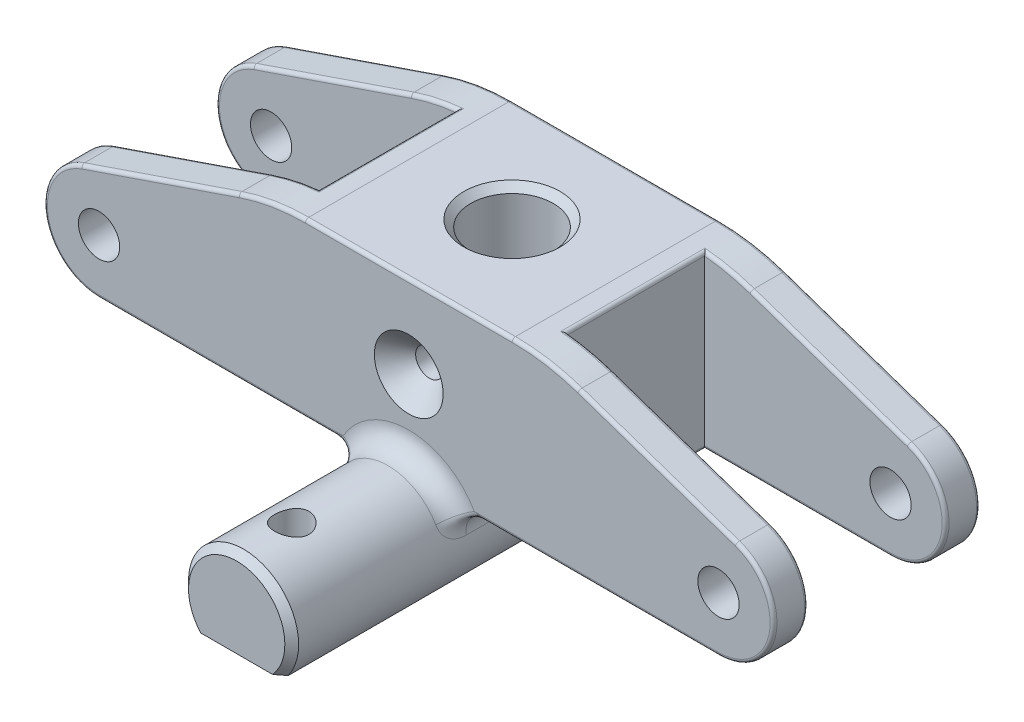
SolidWorks part; units mm, degrees
note: The reader was unsure of these and kept them because the rebuilt part matched: shared geometry of "Sketch2<3>", "Sketch4<3>".
material "Nickel"
ref_plane "Front Plane" through (0, 0, 0) normal (0, 0, 1) x (1, 0, 0)
ref_plane "Top Plane" through (0, 0, 0) normal (0, 1, 0) x (1, 0, 0)
ref_plane "Right Plane" through (0, 0, 0) normal (1, 0, 0) x (0, 0, -1)
sketch "Sketch1" plane through (0, 0, 0) normal (0, 0, 1) x (1, 0, 0)
  line L0 (0, 25) -> (0, 0) construction
  line L1 (-45, 0) -> (45, 0)
  line L2 (-20, 25) -> (20, 25)
  line L3 (20, 25) -> (47.5876, 15.57)
  line L4 (-20, 25) -> (-47.5876, 15.57)
  arc A0 (47.5876, 15.57) -> (45, 0) centre (45, 8) cw
  circle A1 centre (45, 8) radius 3
  circle A2 centre (-45, 8) radius 3
  arc A3 (-47.5876, 15.57) -> (-45, 0) centre (-45, 8) ccw
  dimension "D4" = 8
  dimension "D5" = 6
  dimension "D1" = 20
  dimension "D2" = 25
  dimension "D3" = 45
extrude "Boss-Extrude1" add sketch "Sketch1" along normal mid plane 30
sketch "Sketch2" plane through (0, 0, 0) normal (0, -1, 0) x (1, 0, 0)
  line L0 (0, 32.0671) -> (0, 0) construction
  line L1 (88.0978, 0) -> (-88.0978, 0) construction
  line L2 (-78, 10) -> (-18, 10)
  line L3 (-78, 10) -> (-18, 10)
  line L4 (-78, 10) -> (-78, -10)
  line L5 (-78, -10) -> (-18, -10)
  line L6 (-18, 10) -> (-18, -10)
  line L7 (-78, -10) -> (-18, -10)
  line L8 (-78, 10) -> (-18, 10)
  line L9 (-78, 10) -> (-18, 10)
  line L10 (-78, -10) -> (-18, -10)
  line L11 (-78, -10) -> (-18, -10)
  line L12 (-78, 10) -> (-18, 10)
  line L13 (-78, 10) -> (-18, 10)
  line L14 (-78, -10) -> (-18, -10)
  line L15 (-78, -10) -> (-18, -10)
  line L16 (-78, 10) -> (-18, 10)
  line L17 (-78, 10) -> (-18, 10)
  line L18 (-78, -10) -> (-18, -10)
  line L19 (-78, -10) -> (-18, -10)
  line L20 (78, -10) -> (18, -10)
  line L21 (78, -10) -> (18, -10)
  line L22 (78, 10) -> (18, 10)
  line L23 (78, 10) -> (18, 10)
  line L24 (78, -10) -> (18, -10)
  line L25 (78, -10) -> (18, -10)
  line L26 (78, 10) -> (18, 10)
  line L27 (78, 10) -> (18, 10)
  line L28 (78, -10) -> (18, -10)
  line L29 (78, -10) -> (18, -10)
  line L30 (78, 10) -> (18, 10)
  line L31 (78, 10) -> (18, 10)
  line L32 (78, -10) -> (18, -10)
  line L33 (18, 10) -> (18, -10)
  line L34 (78, -10) -> (18, -10)
  line L35 (78, 10) -> (78, -10)
  line L36 (78, 10) -> (18, 10)
  line L37 (78, 10) -> (18, 10)
  circle A0 centre (0, 0) radius 6
  line M8 (45, -15) -> (45, 15)
  line M10 (-45, 15) -> (-45, -15)
  dimension "D1" = 12
  dimension "D2" = 20
  dimension "D3" = 18
  dimension "D4" = 60
extrude "Cut-Extrude1" cut sketch "Sketch2" against normal through all both and the other way through all contours L6 L2 L5 M10 | L4 L5 L2 M10 | L22 L33 L20 M8 | L35 L22 L20 M8
extrude "Cut-Extrude2" cut sketch "Sketch2<3>" against normal through all from offset 5 contours A0 offset against normal yes
sketch "Sketch2<3>" plane through (0, 0, 0) normal (0, -1, 0) x (1, 0, 0) same geometry as "Sketch2"
fillet "Fillet1" radius 30 2 edges at (20, 25, 12.5) (-20, 25, 12.5)
fillet "Fillet2" radius 0.5 36 edges at (-52.8918, 6.6885, 10) (-36.1526, 19.4787, 10) (-21.4009, 24.3123, 10) (-18, 24.8511, 0) (-21.4009, 24.3123, -10) (-36.1526, 19.4787, -10) (-52.8918, 6.6885, -10) (-31.5, 0, -10) (-18, 0, 0) (-31.5, 0, 10) (36.1526, 19.4787, 10) (52.8918, 6.6885, 10) (31.5, 0, 10) (18, 0, 0) (31.5, 0, -10) (52.8918, 6.6885, -10) (36.1526, 19.4787, -10) (21.4009, 24.3123, -10) (18, 24.8511, 0) (21.4009, 24.3123, 10) (19.9325, 24.5941, -15) (36.1526, 19.4787, -15) (52.8918, 6.6885, -15) (0, 0, -15) (-52.8918, 6.6885, -15) (-36.1526, 19.4787, -15) (-19.9325, 24.5941, -15) (0, 25, -15) (-19.9325, 24.5941, 15) (-36.1526, 19.4787, 15) (-52.8918, 6.6885, 15) (0, 0, 15) (52.8918, 6.6885, 15) (36.1526, 19.4787, 15) (19.9325, 24.5941, 15) (0, 25, 15)
chamfer "Chamfer1" distance 1 angle 45 2 edges at (0, 5, -6) (0, 25, -6)
sketch "Sketch3" plane through (0, 0, 15) normal (0, 0, 1) x (1, 0, 0)
  line L0 (45, 0) -> (-45, 0) construction
  circle A0 centre (0, 13) radius 2
  dimension "D1" = 4
  dimension "D2" = 13
extrude "Cut-Extrude3" cut sketch "Sketch3" against normal through all
chamfer "Chamfer2" distance 3 angle 45 2 edges at (2, 13, -15) (2, 13, 15)
sketch "Sketch4" plane through (0, 0, 0) normal (0, 0, 1) x (1, 0, 0)
  line L1 (45, 0) -> (-45, 0) construction
  line L2 (-6.5, -9.6637) -> (6.5, -9.6637)
  circle A0 centre (0, -5) radius 8
  dimension "D1" = 16
  dimension "D2" = 5
  dimension "D3" = 13
extrude "Boss-Extrude2" add sketch "Sketch4" along normal blind 40 and the other way blind 20 contours L2 A0 | L2 A0
extrude "Cut-Extrude4" cut sketch "Sketch4<3>" along normal blind 70 contours L2 A0
sketch "Sketch4<3>" plane through (0, 0, 0) normal (0, 0, 1) x (1, 0, 0) same geometry as "Sketch4"
fillet "Fillet3" radius 3 8 edges at (6.1857, 0.0731, 14.7604) (-6.1107, 0.1632, 14.8696) (0, 3, 15) (6.245, 0, 0) (-6.245, 0, 0) (6.1107, 0.1632, -14.8696) (-6.1857, 0.0731, -14.7604) (0, 3, -15)
chamfer "Chamfer3" distance 1 angle 45 3 edges at (0, 3, 40) (0, -13, 0) (8, -5, -20)
hole_wizard "Tap Drill for M6 Tap1" positions "Sketch5" profile "Sketch6" hole size "M6" standard "IS" end condition through all
sketch "Sketch5" plane through (0, -9.6637, 0) normal (0, -1, 0) x (-1, 0, 0)
  line L0 (0, -40) -> (0, -32) construction
  line L1 (-5.2202, -40) -> (5.2202, -40) construction
  point P3 (0, -32)
  dimension "D1" = 8
sketch "Sketch6" plane through (0, -9.6637, 32) normal (1, 0, 0) x (0, 0, -1)
  line L0 (0, 0) -> (0, 34.6637)
  line L1 (0, 34.6637) -> (2.5, 34.6637)
  line L2 (2.5, 34.6637) -> (2.5, 0)
  line L5 (2.5, 0) -> (0, 0)
  line L11 (0, -6.35) -> (0, 107.95) construction
  dimension "Thru Hole Dia." = 5
  dimension "Thru Hole Depth" = 34.6637
